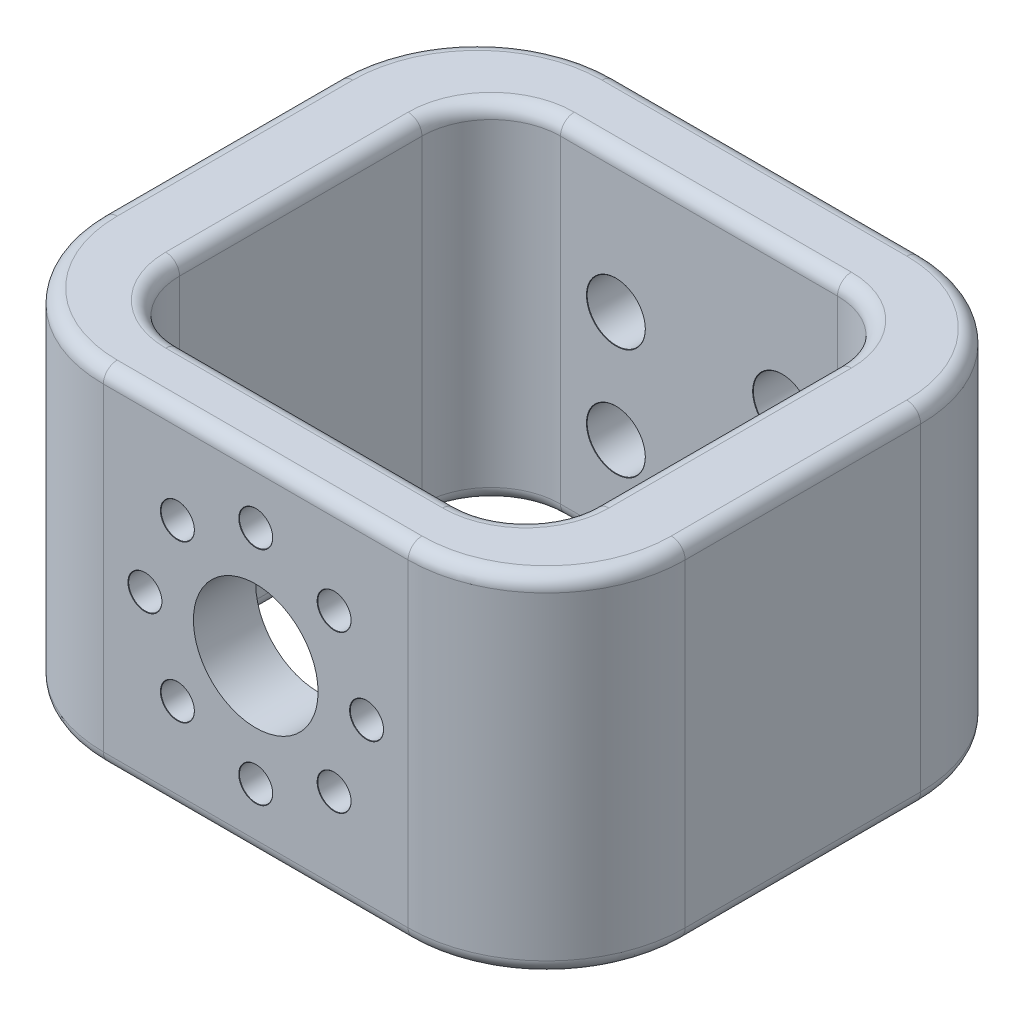
SolidWorks part; units mm, degrees
ref_plane "前视基准面" through (0, 0, 0) normal (0, 0, 1) x (1, 0, 0)
ref_plane "上视基准面" through (0, 0, 0) normal (0, 1, 0) x (1, 0, 0)
ref_plane "右视基准面" through (0, 0, 0) normal (1, 0, 0) x (0, 0, -1)
sketch "草图1" plane through (0, 0, 0) normal (0, 0, 1) x (1, 0, 0)
  line L0 (-15, 0) -> (-15, -29.8122) construction
  line L1 (0, 0) -> (-30, 0)
  line L2 (0, 0) -> (0, -25)
  line L3 (0, -25) -> (-30, -25)
  line L4 (-30, 0) -> (-30, -25)
  line L5 (-50, -12.5) -> (0, -12.5) construction
  dimension "D1" = 30
  dimension "D2" = 25
extrude "凸台-拉伸1" add sketch "草图1" along normal blind 4.5
hole_wizard "M2 间隙孔1" positions "草图2" profile "草图3" hole size "M2" standard "ISO" end condition through all
sketch "草图2" plane through (0, 0, 4.5) normal (0, 0, 1) x (1, 0, 0)
  line L0 (-29, -12.5) -> (0, -12.5) construction
  line L4 (-15, -0.1469) -> (-15, -19.7714) construction
  line L5 (0, 0) -> (-30, 0) construction
  line L6 (-30, -25) -> (0, -25) construction
  line L7 (-30, 0) -> (-30, -25) construction
  line L8 (0, -25) -> (0, 0) construction
  circle A0 centre (-15, -12.5) radius 1.7667 construction
  point P19 (-15, -4.5)
  point P36 (-9.3431, -6.8431)
  point P37 (-7, -12.5)
  point P38 (-9.3431, -18.1569)
  point P39 (-15, -20.5)
  point P40 (-20.6569, -18.1569)
  point P41 (-23, -12.5)
  point P42 (-20.6569, -6.8431)
  dimension "D2" = 8
  dimension "D1" = 8
sketch "草图3" plane through (-20.6569, -6.8431, 4.5) normal (1, 0, 0) x (0, -1, 0)
  line L0 (0, 0) -> (0, 4.5)
  line L1 (0, 4.5) -> (1.2, 4.5)
  line L2 (1.2, 4.5) -> (1.2, 0.025)
  line L3 (1.2, 0.025) -> (1.225, 0)
  line L5 (1.225, 0) -> (0, 0)
  line L6 (-1.2, 0.025) -> (-1.225, 0) construction
  line L11 (0, -6.35) -> (0, 107.95) construction
  dimension "通孔孔直径" = 2.4
  dimension "通孔孔深度" = 4.5
  dimension "近端锥形沉头孔直径" = 2.45
  dimension "近端锥形沉头孔角度" = 90
sketch "草图4" plane through (0, 0, 4.5) normal (0, 0, 1) x (1, 0, 0)
  line L0 (0, -25) -> (0, 0) construction
  line L1 (-30, 0) -> (-36, 0)
  line L2 (-30, 0) -> (-30, -25)
  line L3 (-30, -25) -> (-36, -25)
  line L4 (-36, 0) -> (-36, -25)
  line L5 (-15, 0) -> (-15, -25) construction
  line L7 (0, -25) -> (6, -25)
  line L8 (6, 0) -> (6, -25)
  line L9 (0, 0) -> (0, -25)
  line L10 (0, 0) -> (6, 0)
  dimension "D1" = 6
  dimension "D2" = 25
extrude "凸台-拉伸2" add sketch "草图4" against normal blind 37
sketch "草图6" plane through (0, 0, 4.5) normal (0, 0, 1) x (1, 0, 0)
  line L0 (-20.1769, -12.5) -> (-4.1769, -12.5) construction
  line L1 (-15, -4.5) -> (-15, -20.5) construction
  line L2 (-36, 0) -> (-36, -25) construction
  line L3 (6, -25) -> (6, 0) construction
  circle A0 centre (-15, -12.5) radius 4.5
  dimension "D1" = 9
extrude "切除-拉伸1" cut sketch "草图6" against normal through all
sketch "草图10" plane through (-30, 0, 0) normal (1, 0, 0) x (0, 0, -1)
  line L0 (32.5, -25) -> (0, -25) construction
  line L1 (32.5, 0) -> (27.5, 0)
  line L2 (32.5, 0) -> (32.5, -25)
  line L3 (32.5, -25) -> (27.5, -25)
  line L4 (27.5, 0) -> (27.5, -25)
  dimension "D1" = 5
extrude "凸台-拉伸3" add sketch "草图10" along normal up to surface (30 mm away) up to face at (0, -12.5, -16.25)
hole_wizard "M5 螺纹孔的螺纹孔钻头1" positions "草图12" profile "草图13" hole size "M5" standard "ISO"
sketch "草图12" plane through (0, 0, -27.5) normal (0, 0, 1) x (1, 0, 0)
  line L0 (6, 0) -> (-36, 0) construction
  line L1 (-36, 0) -> (-36, -25) construction
  point P0 (-21, -10)
  point P2 (-9, -10)
  point P4 (-9, -18)
  point P6 (-21, -18)
  dimension "D1" = 10
  dimension "D2" = 8
  dimension "D3" = 10
  dimension "D4" = 8
  dimension "D5" = 12
  dimension "D6" = 15
  dimension "D7" = 0
  dimension "D8" = 0
sketch "草图13" plane through (-21, -10, -27.5) normal (1, 0, 0) x (0, -1, 0)
  line L0 (0, 0) -> (0, 11.2618)
  line L1 (0, 11.2618) -> (2.1, 10)
  line L2 (2.1, 10) -> (2.1, 0.025)
  line L3 (2.1, 0.025) -> (2.125, 0)
  line L5 (2.125, 0) -> (0, 0)
  line L6 (-2.1, 0.025) -> (-2.125, 0) construction
  line L10 (0, 11.2618) -> (-2.1, 10) construction
  line L11 (0, -6.35) -> (0, 107.95) construction
  dimension "孔直径" = 4.2
  dimension "孔深度" = 10
  dimension "近端锥形沉头孔直径" = 4.25
  dimension "近端锥形沉头孔角度" = 90
  dimension "导头角度" = 118
sketch "草图7" plane through (-36, 0, 0) normal (-1, 0, 0) x (0, 0, 1)
  line L0 (3.975, -12.5) -> (-6.8427, -12.5) construction
  line L1 (-32.5, 0) -> (-32.5, -25) construction
  point P6 (-27.5, -16.5)
  point P8 (-27.5, -40.5)
  point P10 (-15.5, -16.5)
  point P12 (-15.5, -40.5)
  dimension "D1" = 4
  dimension "D2" = 4
  dimension "D3" = 24
  dimension "D4" = 28
  dimension "D5" = 5
  dimension "D6" = 12
  dimension "D7" = 12
  dimension "D8" = 5
fillet "圆角1" radius 5 4 edges at (-30, -12.5, 0) (0, -12.5, 0) (0, -12.5, -27.5) (-30, -12.5, -27.5)
fillet "圆角2" radius 10 4 edges at (-36, -12.5, 4.5) (6, -12.5, 4.5) (6, -12.5, -32.5) (-36, -12.5, -32.5)
fillet "圆角4" radius 1 32 edges at (3.0711, -25, 1.5711) (6, -25, -14) (3.0711, -25, -29.5711) (-15, -25, -32.5) (-33.0711, -25, -29.5711) (-36, -25, -14) (-33.0711, -25, 1.5711) (-15, -25, 4.5) (-1.4645, -25, -1.4645) (-15, -25, 0) (-28.5355, -25, -1.4645) (-30, -25, -13.75) (-28.5355, -25, -26.0355) (-15, -25, -27.5) (-1.4645, -25, -26.0355) (0, -25, -13.75) (-33.0711, 0, -29.5711) (-15, 0, -32.5) (3.0711, 0, -29.5711) (6, 0, -14) (3.0711, 0, 1.5711) (-15, 0, 4.5) (-33.0711, 0, 1.5711) (-36, 0, -14) (-28.5355, 0, -1.4645) (-15, 0, 0) (-1.4645, 0, -1.4645) (0, 0, -13.75) (-1.4645, 0, -26.0355) (-15, 0, -27.5) (-28.5355, 0, -26.0355) (-30, 0, -13.75)
